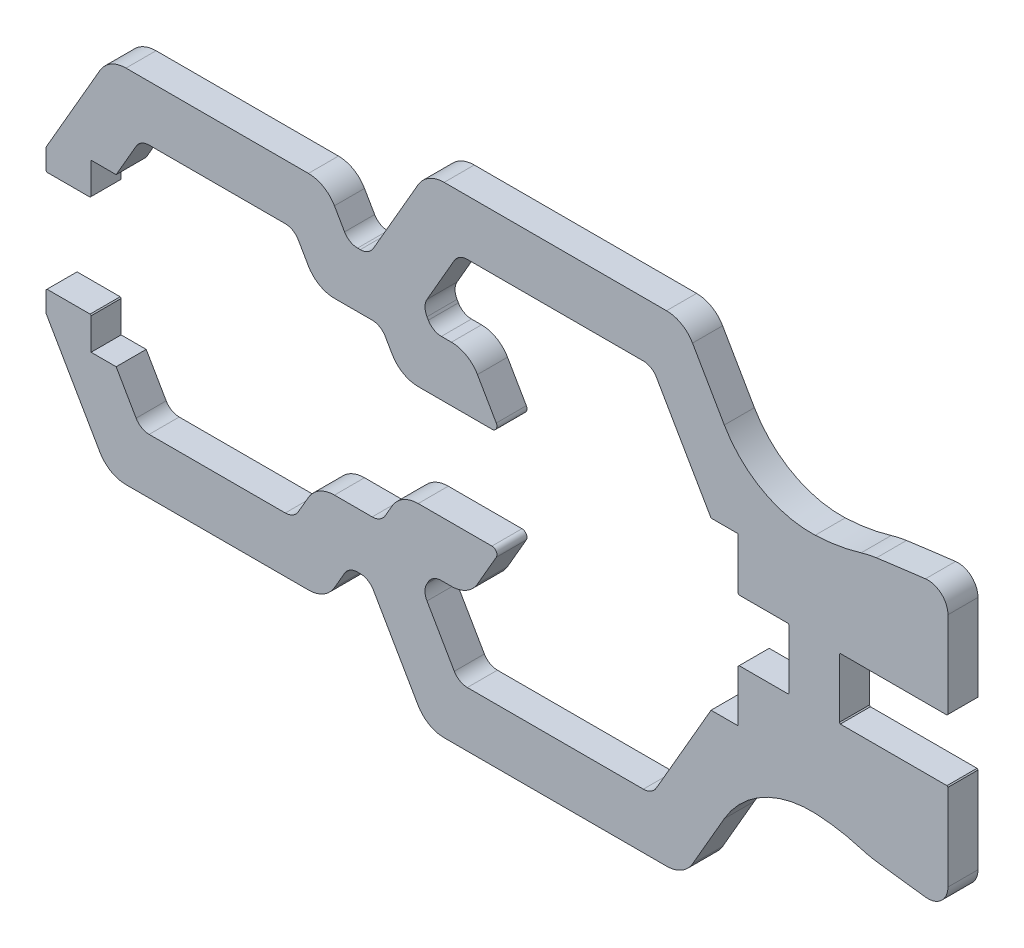
SolidWorks part; units mm, degrees
ref_plane "前视基准面" through (0, 0, 0) normal (0, 0, 1) x (1, 0, 0)
ref_plane "上视基准面" through (0, 0, 0) normal (0, 1, 0) x (1, 0, 0)
ref_plane "右视基准面" through (0, 0, 0) normal (1, 0, 0) x (0, 0, -1)
ref_axis "基准轴1" through (-271.0774, 0, 0) along (1, 0, 0)
sketch "草图1" plane through (0, 0, 0) normal (0, 0, 1) x (1, 0, 0)
  line L0 (-19.6441, 0) -> (19.6441, 0) construction
  line L1 (9, 65) -> (3.5939, 47)
  line L2 (3.5939, 47) -> (12.8315, 31)
  line L3 (12.8315, 31) -> (-1.2116, 31)
  line L4 (-1.2116, 31) -> (-3.4641, 23.5)
  line L5 (-7.7942, 31) -> (0, 17.5)
  line L6 (80, -11.5) -> (380, -7.1666)
  line L7 (0, -17.5) -> (24, -17)
  line L9 (-1.2116, -31) -> (-3.4641, -23.5)
  line L10 (12.8315, -31) -> (-1.2116, -31)
  line L11 (3.5939, -47) -> (12.8315, -31)
  line L12 (9, -65) -> (3.5939, -47)
  line L13 (9, 65) -> (3, 65)
  line L14 (3, 65) -> (-7.3923, 47)
  line L15 (-7.3923, 47) -> (-26.859, 35.7609)
  line L16 (-26.859, 35.7609) -> (-40, 13)
  line L17 (-26.859, -35.7609) -> (-40, -13)
  line L18 (-7.3923, -47) -> (-26.859, -35.7609)
  line L19 (3, -65) -> (-7.3923, -47)
  line L20 (9, -65) -> (3, -65)
  line L21 (-95, 16) -> (-95, -16) construction
  line L22 (-150, 13) -> (-156.3509, 24)
  line L23 (-156.3509, 24) -> (-182, 24)
  line L24 (-150, -13) -> (-156.3509, -24)
  line L25 (-156.3509, -24) -> (-182, -24)
  line L26 (-182, 24) -> (-187.7735, 14)
  line L27 (-187.7735, 14) -> (-189.7735, 14)
  line L28 (-189.7735, 14) -> (-192.0829, 18)
  line L29 (-192.0829, 18) -> (-213.7506, 18)
  line L30 (-213.7506, 18) -> (-220, 7.1756)
  line L31 (-213.7506, -18) -> (-220, -7.1756)
  line L32 (-192.0829, -18) -> (-213.7506, -18)
  line L33 (-189.7735, -14) -> (-192.0829, -18)
  line L34 (-187.7735, -14) -> (-189.7735, -14)
  line L35 (-182, -24) -> (-187.7735, -14)
  line L36 (0, 17.5) -> (0, -17.5) construction
  line L37 (0, 17.5) -> (24, 17)
  line L38 (80, 11.5) -> (380, 7.1666)
  line L39 (680, 5) -> (780, 5)
  line L40 (680, -5) -> (780, -5)
  line L41 (780, 5) -> (780, -5)
  line L42 (3.0165, 36) -> (-1.3488, 43.561)
  line L43 (-1.3488, 43.561) -> (-14.4449, 36)
  line L44 (-14.4449, 36) -> (3.0165, 36)
  line L45 (-1.3488, -43.561) -> (-14.4449, -36)
  line L46 (3.0165, -36) -> (-1.3488, -43.561)
  line L47 (-14.4449, -36) -> (3.0165, -36)
  line L48 (-7.7942, 31) -> (-29.6077, 31)
  line L49 (-7.7942, -31) -> (-29.6077, -31)
  line L50 (-7.7942, -31) -> (0, -17.5)
  line L53 (-195.2583, -12.5) -> (-210.5751, -12.5)
  line L62 (-210.5751, -12.5) -> (-213, -8.3)
  line L77 (-195.2583, 12.5) -> (-210.5751, 12.5)
  line L80 (-210.5751, 12.5) -> (-213, 8.3)
  line L108 (-182.4145, -12.2821) -> (-178.8246, -18.5)
  line L109 (-178.8246, -18.5) -> (-159.5263, -18.5)
  line L110 (-159.5263, -18.5) -> (-153.6373, -8.3)
  line L111 (-153.6373, -8.3) -> (-153.6373, -3.05) construction
  line L115 (-182.4145, 12.2821) -> (-178.8246, 18.5)
  line L116 (-178.8246, 18.5) -> (-159.5263, 18.5)
  line L117 (-159.5263, 18.5) -> (-153.6373, 8.3)
  line L118 (-184.5899, -5.05) -> (-186.5818, -8.5)
  line L119 (-186.5818, -8.5) -> (-192.9489, -8.5)
  line L120 (-192.9489, -8.5) -> (-195.2583, -12.5)
  line L123 (-192.9489, 8.5) -> (-195.2583, 12.5)
  line L124 (-182.4145, -12.2821) -> (-181.4145, -10.55)
  line L125 (-181.4145, -10.55) -> (-177.8127, -10.55)
  line L126 (-177.8127, -10.55) -> (-174.6373, -5.05)
  line L127 (-174.6373, -5.05) -> (-184.5899, -5.05)
  line L128 (-186.5818, 8.5) -> (-192.9489, 8.5)
  line L129 (-177.8127, 10.55) -> (-174.6373, 5.05)
  line L130 (-174.6373, 5.05) -> (-184.5899, 5.05)
  line L131 (-184.5899, 5.05) -> (-186.5818, 8.5)
  line L132 (-182.4145, 12.2821) -> (-181.4145, 10.55)
  line L133 (-181.4145, 10.55) -> (-177.8127, 10.55)
  line L135 (-220, 7.1756) -> (-220, 5.05)
  line L136 (-213, 8.3) -> (-215.5, 8.3)
  line L137 (-215.5, 8.3) -> (-215.5, 5.05)
  line L138 (-215.5, 5.05) -> (-220, 5.05)
  line L139 (-215.5, -5.05) -> (-220, -5.05)
  line L140 (-215.5, -8.3) -> (-215.5, -5.05)
  line L141 (-213, -8.3) -> (-215.5, -8.3)
  line L142 (-150.9373, -3.05) -> (-145.8373, -3.05)
  line L143 (-145.8373, -3.05) -> (-145.8373, 3.05)
  line L144 (-220, 5.05) -> (-220, 0) construction
  line L145 (-220, -5.05) -> (-220, -7.1756)
  line L146 (-150.9373, 3.05) -> (-145.8373, 3.05)
  line L147 (-220, 0) -> (-220, -5.05) construction
  line L148 (-153.6373, -3.05) -> (-153.6373, 0) construction
  line L149 (-153.6373, 3.05) -> (-153.6373, 8.3) construction
  line L150 (-153.6373, 0) -> (-153.6373, 3.05) construction
  line L151 (-130, -14.0157) -> (-130, -3.05)
  line L152 (-130, -3.05) -> (-140.8373, -3.05)
  line L153 (-140.8373, -3.05) -> (-140.8373, 3.05)
  line L154 (-140.8373, 3.05) -> (-130, 3.05)
  line L155 (-130, -3.05) -> (-130, 0) construction
  line L156 (-130, 3.05) -> (-130, 14.0157)
  line L157 (-130, 0) -> (-130, 3.05) construction
  line L158 (-153.6373, -8.3) -> (-150.9373, -8.3)
  line L159 (-150.9373, -8.3) -> (-150.9373, -3.05)
  line L160 (-153.6373, 8.3) -> (-150.9373, 8.3)
  line L161 (-150.9373, 8.3) -> (-150.9373, 3.05)
  line L162 (-153.6373, -3.05) -> (-150.9373, -3.05) construction
  line L163 (-153.6373, 3.05) -> (-150.9373, 3.05) construction
  arc A0 (-40, 13) -> (-52, 13) centre (-46, 30.5) cw
  arc A1 (-40, -13) -> (-52, -13) centre (-46, -30.5) ccw
  arc A2 (-52, 13) -> (-138, 13) centre (-95, -293.6667) ccw
  arc A3 (-52, -13) -> (-138, -13) centre (-95, 293.6667) cw
  arc A4 (-150, -13) -> (-138, -13) centre (-144, -30.5) cw
  arc A5 (-150, 13) -> (-138, 13) centre (-144, 30.5) ccw
  arc A6 (24, 17) -> (36, 14) centre (40.2074, 56.3296) ccw
  arc A7 (36, 14) -> (80, 11.5) centre (87.5238, 532.3687) ccw
  arc A8 (36, -14) -> (80, -11.5) centre (87.5238, -532.3687) cw
  arc A9 (24, -17) -> (36, -14) centre (40.2074, -56.3296) cw
  arc A10 (380, 7.1666) -> (680, 5) centre (680, 20776.0363) ccw
  arc A11 (380, -7.1666) -> (680, -5) centre (680, -20776.0363) cw
  point P30 (-46, 12)
  point P31 (-46, -12)
  point P117 (-145.8373, 0)
  dimension "D4" = 24
  dimension "D5" = 24
  dimension "D15" = 34
  dimension "D17" = 16.6
  dimension "D1" = 130
  dimension "D2" = 35
  dimension "D3" = 120
  dimension "D6" = 220
  dimension "D7" = 40
  dimension "D8" = 150
  dimension "D9" = 36
  dimension "D10" = 32
  dimension "D11" = 48
  dimension "D12" = 120
  dimension "D13" = 12
  dimension "D14" = 120
  dimension "D16" = 26
  dimension "D18" = 100
  dimension "D19" = 10
  dimension "D20" = 23
  dimension "D21" = 28
  dimension "D22" = 80
  dimension "D23" = 12
  dimension "D24" = 300
  dimension "D25" = 2
  dimension "D26" = 28
  dimension "D27" = 7
  dimension "D28" = 34
  dimension "D29" = 30
  dimension "D30" = 18
  dimension "D31" = 30
  dimension "D32" = 9
  dimension "D33" = 7.5
  dimension "D34" = 6
  dimension "D35" = 6
  dimension "D36" = 6
  dimension "D37" = 5
  dimension "D38" = 5.5
  dimension "D39" = 5.5
  dimension "D40" = 5.5
  dimension "D41" = 5.5
  dimension "D42" = 5.5
  dimension "D43" = 5.5
  dimension "D44" = 5.5
  dimension "D45" = 5.5
  dimension "D46" = 10.1
  dimension "D47" = 2
  dimension "D48" = 5.5
  dimension "D49" = 21
  dimension "D50" = 38
  dimension "D51" = 10.1
  dimension "D52" = 4.5
  dimension "D53" = 1000
  dimension "D54" = 6.1
  dimension "D55" = 16.6
  dimension "D56" = 90
  dimension "D57" = 5.1
  dimension "D58" = 5
  dimension "D59" = 2.7
extrude "凸台-拉伸1" add sketch "草图1" along normal mid plane 3 contours A5 L22 L23 L26 L27 L28 L29 L30 L135 L138 L137 L136 L80 L77 L123 L128 L131 L130 L129 L133 L132 L115 L116 L117 L149 L146 L143 L142 L111 L110 L109 L108 L124 L125 L126 L127 L118 L119 L120 L53 L62 L141 L140 L139 L145 L31 L32 L33 L34 L35 L25 region at (-131.02, 8.5329, 0)
fillet "圆角4" radius 10 4 edges at (-138, -13, 0) (-138, 13, 0) (-150, 13, 0) (-150, -13, 0)
fillet "圆角7" radius 1.5 18 edges at (-210.5751, 12.5, 0) (-210.5751, -12.5, 0) (-195.2583, -12.5, 0) (-186.5818, 8.5, 0) (-195.2583, 12.5, 0) (-178.8246, 18.5, 0) (-159.5263, 18.5, 0) (-159.5263, -18.5, 0) (-178.8246, -18.5, 0) (-186.5818, -8.5, 0) (-182.4145, 12.2821, 0) (-181.4145, 10.55, 0) (-181.4145, -10.55, 0) (-182.4145, -12.2821, 0) (-189.7735, -14, 0) (-187.7735, -14, 0) (-187.7735, 14, 0) (-189.7735, 14, 0)
fillet "圆角8" radius 3 14 edges at (-213.7506, 18, 0) (-213.7506, -18, 0) (-192.0829, -18, 0) (-192.0829, 18, 0) (-177.8127, 10.55, 0) (-177.8127, -10.55, 0) (-184.5899, 5.05, 0) (-192.9489, 8.5, 0) (-192.9489, -8.5, 0) (-184.5899, -5.05, 0) (-182, 24, 0) (-156.3509, 24, 0) (-156.3509, -24, 0) (-182, -24, 0)
chamfer "倒角1" distance 0.1 angle 45 12 edges at (-145.8373, 3.05, 0) (-145.8373, -3.05, 0) (-140.8373, -3.05, 0) (-140.8373, 3.05, 0) (-150.9373, -3.05, 0) (-150.9373, 3.05, 0) (-130, -3.05, 0) (-130, 3.05, 0) (-220, -5.05, 0) (-215.5, -5.05, 0) (-215.5, 5.05, 0) (-220, 5.05, 0)
fillet "圆角9" radius 2 2 edges at (-130, -14.0157, 0) (-130, 14.0157, 0)
fillet "圆角10" radius 0.5 2 edges at (-174.6373, -5.05, 0) (-174.6373, 5.05, 0)
